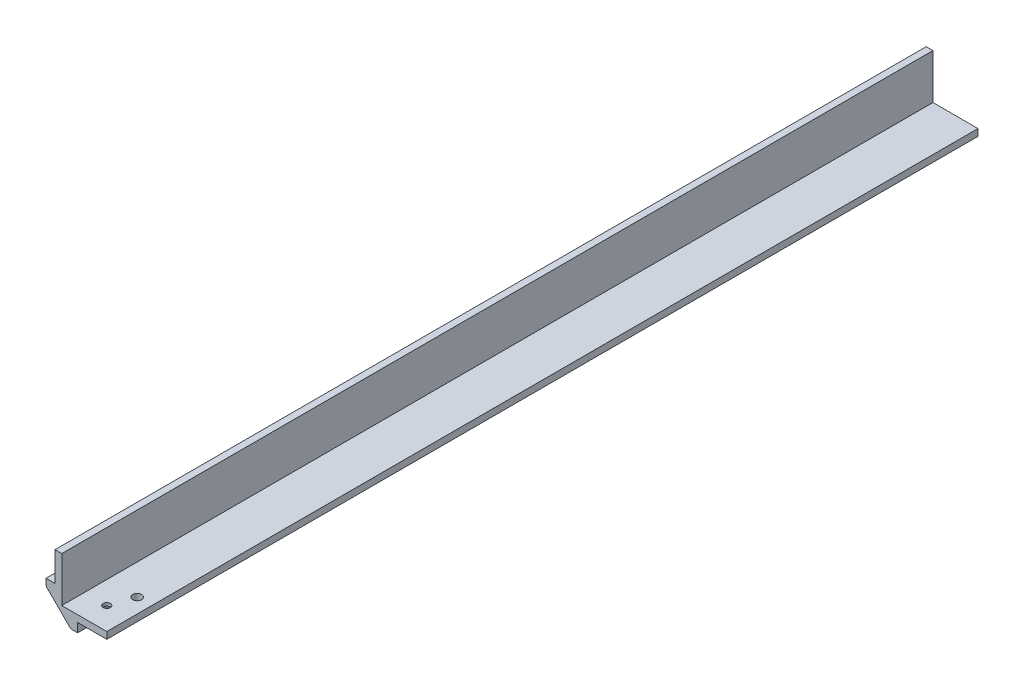
SolidWorks part; units mm, degrees
ref_plane "Front Plane" through (0, 0, 0) normal (0, 0, 1) x (1, 0, 0)
ref_plane "Top Plane" through (0, 0, 0) normal (0, 1, 0) x (1, 0, 0)
ref_plane "Right Plane" through (0, 0, 0) normal (1, 0, 0) x (0, 0, -1)
ref_plane "Plane1" through (0, 0, 280) normal (0, 0, 1) x (1, 0, 0)
sketch "Sketch1" plane through (0, 0, 280) normal (0, 0, 1) x (1, 0, 0)
  line L0 (-7, 4) -> (4, -7)
  line L1 (4, -7) -> (7, -7)
  line L2 (7, -7) -> (7, -3)
  line L3 (7, -3) -> (20, -3)
  line L4 (20, -3) -> (20, 0)
  line L5 (20, 0) -> (0, 0)
  line L6 (0, 0) -> (0, 20)
  line L7 (0, 20) -> (-3, 20)
  line L8 (-3, 20) -> (-3, 7)
  line L9 (-3, 7) -> (-7, 7)
  line L10 (-7, 7) -> (-7, 4)
extrude "Boss-Extrude1" add sketch "Sketch1" against normal blind 386.9
sketch "Sketch2" plane through (0, -3, 0) normal (0, -1, 0) x (1, 0, 0)
  line L0 (20, -106.9) -> (20, 280) construction
  line L1 (55, 280) -> (-55, 280) construction
  point P0 (10, 270)
  dimension "D1" = 10
  dimension "D2" = 10
hole_wizard "CBORE for M3 SBHCS1" positions "Sketch2" profile "Sketch3" counterbore size "M3" standard "ANSI Metric" end condition through all
sketch "Sketch3" plane through (10, -3, 270) normal (1, 0, 0) x (0, 0, -1)
  line L0 (0, 0) -> (0, 23)
  line L1 (0, 23) -> (1.6, 23)
  line L3 (1.6, 23) -> (1.6, 1.65)
  line L4 (1.6, 1.65) -> (3, 1.65)
  line L5 (3, 1.65) -> (3, 0)
  line L7 (3, 0) -> (0, 0)
  line L11 (0, -6.35) -> (0, 107.95) construction
  dimension "Thru Hole Dia." = 3.2
  dimension "Thru Hole Depth" = 23
  dimension "C'Bore Dia." = 6
  dimension "C'Bore Depth" = 1.65
sketch "Sketch4" plane through (0, -3, 0) normal (0, -1, 0) x (1, 0, 0)
  line L0 (20, -106.9) -> (20, 280) construction
  line L1 (55, 280) -> (-55, 280) construction
  circle A0 centre (13.5, 260) radius 2
  point P0 (13.5, 260)
  dimension "D3" = 4
  dimension "D1" = 6.5
  dimension "D2" = 20
extrude "Cut-Extrude1" cut sketch "Sketch4" against normal blind 10
fillet "Fillet1" radius 1.5 2 edges at (-7, 4, 86.55) (4, -7, 86.55)
